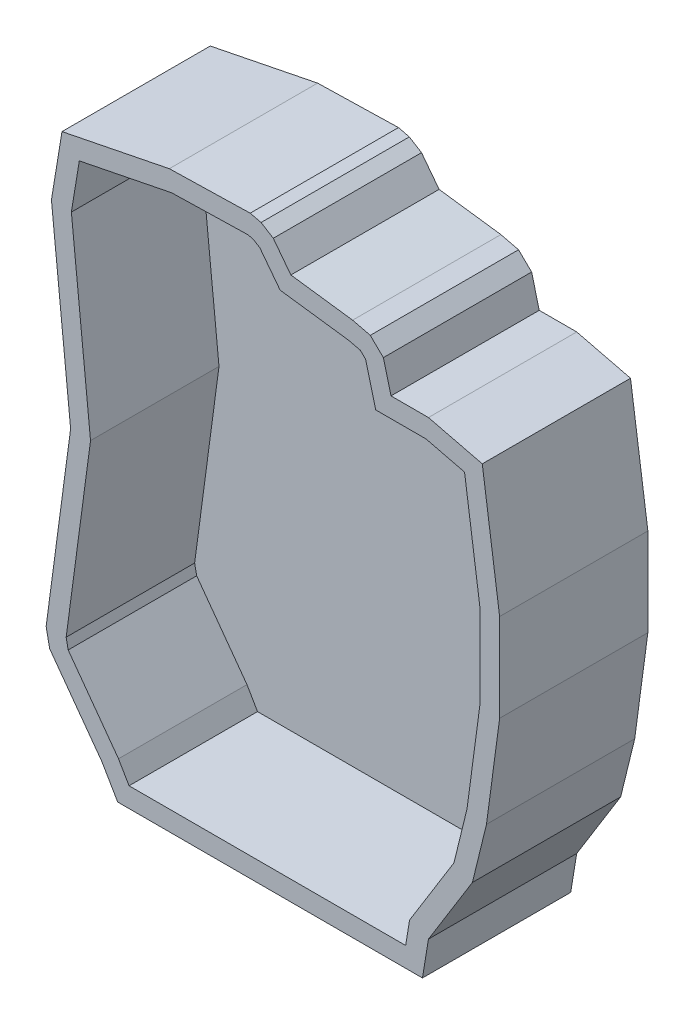
SolidWorks part; units mm, degrees
ref_plane "Front Plane" through (0, 0, 0) normal (0, 0, 1) x (1, 0, 0)
ref_plane "Top Plane" through (0, 0, 0) normal (0, 1, 0) x (1, 0, 0)
ref_plane "Right Plane" through (0, 0, 0) normal (1, 0, 0) x (0, 0, -1)
sketch "Sketch1" plane through (0, 0, 0) normal (0, 0, 1) x (1, 0, 0)
  line L0 (6.2196, 20.172) -> (31.0978, 20.172) construction
  line L16 (546.873, 9.9176) -> (893.0858, 9.9176) construction
  line L17 (543.5946, 13.7694) -> (705.2646, 13.7694) construction
  line L43 (547.2066, 9.9086) -> (608.8766, 9.9086) construction
  line L44 (546.5809, 9.8961) -> (608.2509, 9.8961)
  line L45 (608.2509, 9.8961) -> (609.4687, 17.3252)
  line L46 (609.4687, 17.3252) -> (618.3641, 31.6987)
  line L47 (618.3641, 31.6987) -> (621.2095, 43.3087)
  line L48 (621.2095, 43.3087) -> (623.8684, 63.2242)
  line L49 (623.8684, 63.2242) -> (623.8684, 81.0545)
  line L50 (623.8684, 81.0545) -> (620.3573, 106.0595)
  line L51 (620.3573, 106.0595) -> (609.4687, 108.7281)
  line L52 (609.4687, 108.7281) -> (601.8876, 108.7281)
  line L53 (601.8876, 108.7281) -> (600.3424, 114.6689)
  line L54 (600.3424, 114.6689) -> (597.6933, 117.2443)
  line L55 (597.6933, 117.2443) -> (594.1218, 118.1197)
  line L56 (594.1218, 118.1197) -> (581.6232, 119.7883)
  line L57 (581.6232, 119.7883) -> (578.0652, 124.4428)
  line L58 (578.0652, 124.4428) -> (575.593, 125.9728)
  line L59 (575.593, 125.9728) -> (573.398, 126.5107)
  line L60 (573.398, 126.5107) -> (557.03, 126.1181)
  line L61 (557.03, 126.1181) -> (535.3097, 121.7603)
  line L62 (535.3097, 121.7603) -> (533.8832, 113.0576)
  line L63 (533.8832, 113.0576) -> (533.1735, 108.7281)
  line L64 (533.1735, 108.7281) -> (536.3202, 77.7869)
  line L65 (536.3202, 77.7869) -> (537.0549, 70.5624)
  line L66 (537.0549, 70.5624) -> (532.0987, 33.4394)
  line L67 (532.0987, 33.4394) -> (532.8106, 29.8912)
  line L68 (532.8106, 29.8912) -> (543.389, 15.3737)
  line L69 (543.389, 15.3737) -> (546.5809, 9.8961)
  dimension "D1" = 61.67
  dimension "D2" = 61.67
extrude "Boss-Extrude1" add sketch "Sketch1" along normal blind 30
ref_plane "Plane1" through (530, 0, 0) normal (1, 0, 0) x (0, 0, -1)
sketch "Sketch2" plane through (530, 0, 0) normal (1, 0, 0) x (0, 0, -1)
  line L0 (-24.212, 126.5107) -> (-24.212, 90.6107)
  line L1 (-30, 126.5107) -> (0, 126.5107) construction
  line L2 (-24.212, 90.6107) -> (-30, 81.3731)
  line L3 (-30, 108.7281) -> (-30, 70.5624) construction
  line L4 (-24.212, 90.6107) -> (-24.212, 79.6081) construction
  line L5 (-24.212, 126.5107) -> (-30, 126.5107)
  line L7 (-30, 126.5107) -> (-30, 81.3731)
  dimension "D1" = 35.9
  dimension "D2" = 5.788
  dimension "D3" = 32.07
shell "Shell1" thickness 4 removed face at (581.4595, 80.5225, 30)
ref_plane "Plane2" through (0, 0, 30) normal (0, 0, 1) x (1, 0, 0)
sketch "Sketch4" plane through (0, 0, 30) normal (0, 0, 1) x (1, 0, 0)
  line L0 (548.1421, 120.2552) -> (553.3063, 94.4672) construction
  line L1 (557.4748, 122.1276) -> (538.8094, 118.3827) construction
  line L3 (546.9333, 93.1885) -> (554.0131, 57.3817)
  line L4 (554.0131, 57.3817) -> (566.7662, 59.9033)
  line L5 (566.7662, 59.9033) -> (559.6864, 95.7101)
  line L7 (546.9333, 93.1885) -> (559.6864, 95.7101)
  line L8 (573.5848, 122.3466) -> (573.5848, 96.0466) construction
  line L9 (596.3921, 87.5623) -> (591.562, 51.3833)
  line L10 (593.4606, 114.7225) -> (589.9493, 88.4225) construction
  line L11 (611.83, 104.0311) -> (605.5695, 78.487) construction
  line L13 (567.0848, 96.0466) -> (567.0848, 59.5466)
  line L14 (567.0848, 59.5466) -> (580.0848, 59.5466)
  line L15 (580.0848, 59.5466) -> (580.0848, 96.0466)
  line L17 (567.0848, 96.0466) -> (580.0848, 96.0466)
  line L18 (593.3789, 114.1833) -> (579.4516, 116.0428) construction
  line L19 (583.5065, 89.2827) -> (596.3921, 87.5623)
  line L20 (574.0261, 122.2384) -> (572.9623, 122.4991) construction
  line L21 (583.5065, 89.2827) -> (578.6763, 53.1037)
  line L22 (578.6763, 53.1037) -> (591.562, 51.3833)
  line L23 (616.773, 102.8196) -> (608.9857, 104.7281) construction
  line L25 (599.2563, 80.0343) -> (590.5678, 44.5835)
  line L26 (590.5678, 44.5835) -> (603.1941, 41.489)
  line L27 (603.1941, 41.489) -> (611.8826, 76.9398)
  line L29 (599.2563, 80.0343) -> (611.8826, 76.9398)
  point P8 (553.3098, 94.4493)
  point P16 (589.9493, 88.4225)
  point P19 (573.5848, 96.0466)
  point P35 (605.5695, 78.487)
  dimension "D1" = 26.3
  dimension "D2" = 13
  dimension "D3" = 36.5
  dimension "D4" = 26.3
  dimension "D5" = 13
  dimension "D6" = 36.5
  dimension "D7" = 26.3
  dimension "D8" = 26.3
  dimension "D9" = 36.5
  dimension "D10" = 13
  dimension "D11" = 13
  dimension "D12" = 36.5
  dimension "D13" = 26.3
  dimension "D14" = 13
  dimension "D15" = 36.5
